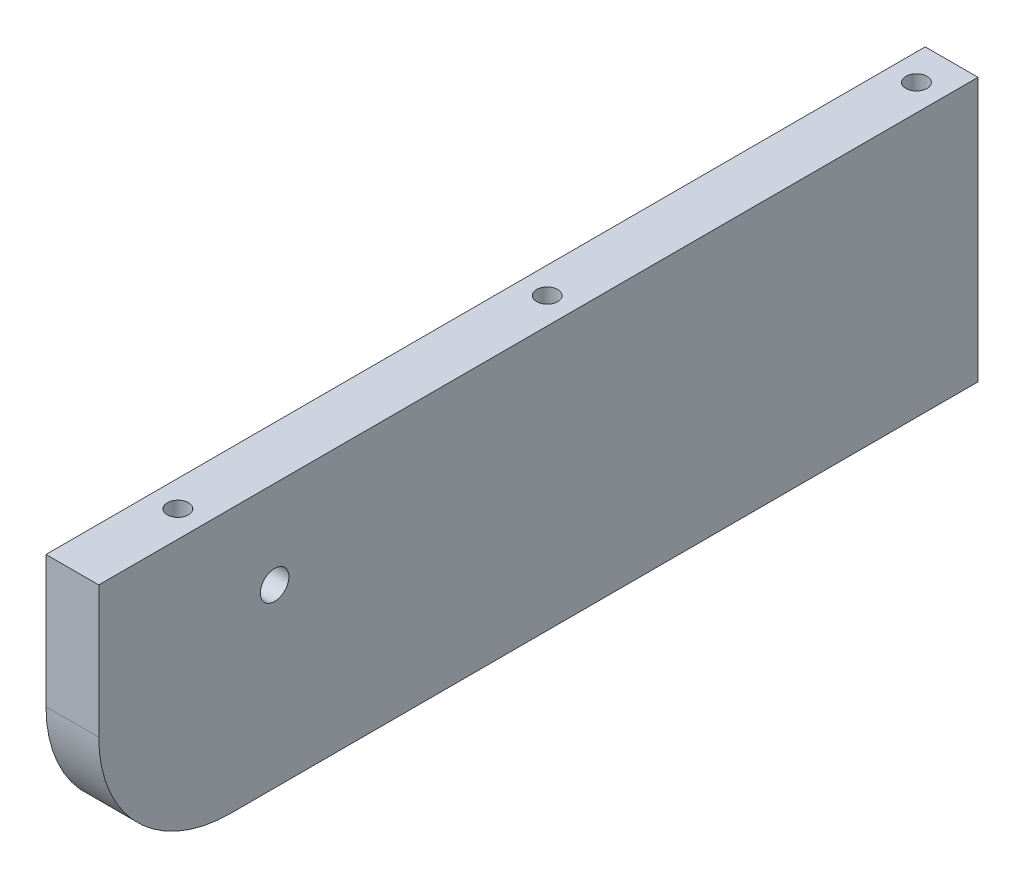
SolidWorks part; units mm, degrees
ref_plane "Front Plane" through (0, 0, 0) normal (0, 0, 1) x (1, 0, 0)
ref_plane "Top Plane" through (0, 0, 0) normal (0, 1, 0) x (1, 0, 0)
ref_plane "Right Plane" through (0, 0, 0) normal (1, 0, 0) x (0, 0, -1)
sketch "Sketch1" plane through (0, 0, 0) normal (1, 0, 0) x (0, 0, -1)
  line L1 (-50, -15) -> (50, -15)
  line L2 (-50, -15) -> (-50, 15)
  line L3 (-50, 15) -> (50, 15)
  line L4 (50, -15) -> (50, 15)
  line L5 (-50, -15) -> (50, 15) construction
  line L6 (-50, 15) -> (50, -15) construction
  circle A0 centre (-30, 5) radius 1.625
  point P0 (0, 0)
  dimension "D3" = 3.25
  dimension "D1" = 30
  dimension "D2" = 100
  dimension "D4" = 20
  dimension "D5" = 10
extrude "Boss-Extrude1" add sketch "Sketch1" along normal blind 6 contours L1 L4 L3 L2 A0 | A0 region at (0, -0.0139, -0.0832)
fillet "Fillet1" radius 15 1 edges at (3, -15, 50)
hole_wizard "CBORE for M2 SHCS1" positions "Sketch4" profile "Sketch5" counterbore size "M2" standard "ANSI Metric"
sketch "Sketch4" plane through (-724.2935, 25, -1323.2827) normal (0, 1, 0) x (1, 0, 0)
  line L3 (625.2935, -1277.2827) -> (625.2935, -1361.2827) construction
  line L5 (727.2935, -1277.2827) -> (727.2935, -1361.2827) construction
  circle A0 centre (727.2935, -1277.2827) radius 2.243
  circle A1 centre (727.2935, -1361.2827) radius 2.2384
  circle A3 centre (625.2935, -1277.2827) radius 2.3325
  circle A4 centre (625.2935, -1361.2827) radius 1.7576
  circle A5 centre (625.2935, -1319.2827) radius 1.8624
  circle A6 centre (727.2935, -1319.2827) radius 2.0271
  point P1 (727.2935, -1277.2827)
  point P8 (727.2935, -1361.2827)
  point P15 (625.2935, -1277.2827)
  point P17 (625.2935, -1361.2827)
  point P19 (625.2935, -1319.2827)
  point P27 (727.2935, -1319.2827)
sketch "Sketch5" plane through (3, 25, -46) normal (1, 0, 0) x (0, 0, 1)
  line L0 (0, 0) -> (0, 20.721)
  line L1 (0, 20.721) -> (1.2, 20)
  line L2 (1.2, 20) -> (1.2, 2)
  line L3 (1.2, 2) -> (2.2, 2)
  line L4 (2.2, 2) -> (2.2, 0)
  line L5 (2.2, 0) -> (0, 0)
  line L6 (0, 20.721) -> (-1.2, 20) construction
  line L7 (0, -6.35) -> (0, 107.95) construction
  dimension "Hole Dia." = 2.4
  dimension "Hole Depth" = 20
  dimension "C'Bore Dia." = 4.4
  dimension "C'Bore Depth" = 2
  dimension "Drill Angle" = 118
